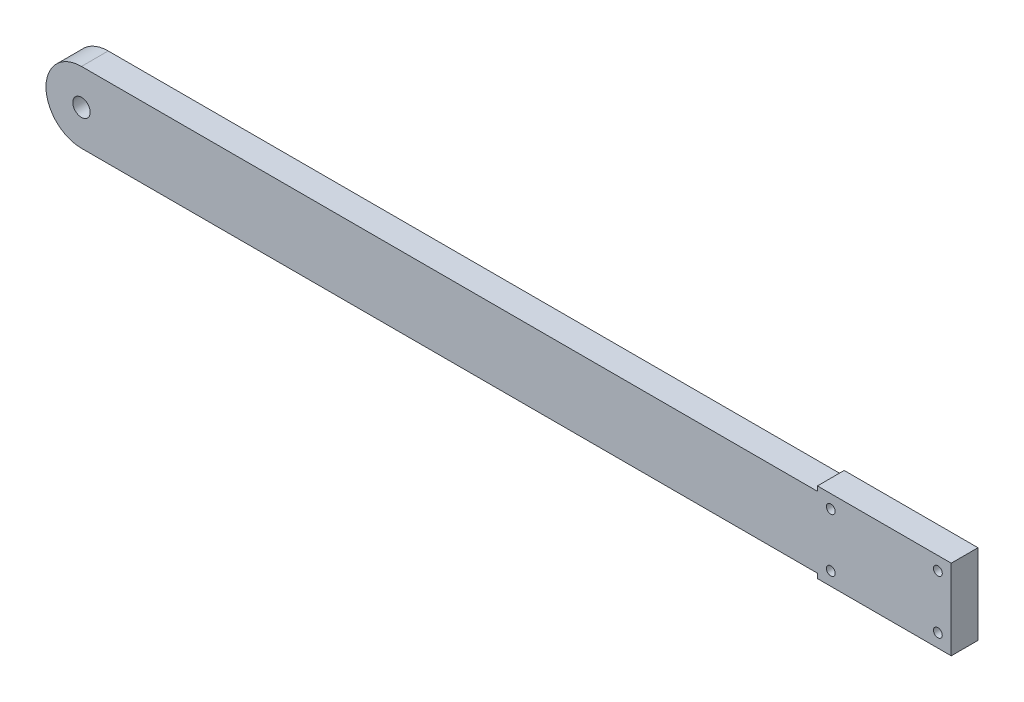
SolidWorks part; units mm, degrees
ref_plane "Front Plane" through (0, 0, 0) normal (0, 0, 1) x (1, 0, 0)
ref_plane "Top Plane" through (0, 0, 0) normal (0, 1, 0) x (1, 0, 0)
ref_plane "Right Plane" through (0, 0, 0) normal (1, 0, 0) x (0, 0, -1)
sketch "Sketch1" plane through (0, 0, 0) normal (0, 0, 1) x (1, 0, 0)
  line L0 (0, 0) -> (300, 0) construction
  line L1 (0, 13.25) -> (300, 13.25)
  line L2 (0, -13.25) -> (300, -13.25)
  line L3 (280, 10) -> (320, 10) construction
  line L4 (275, -15) -> (325, -15)
  line L5 (275, -15) -> (275, 15)
  line L6 (275, 15) -> (325, 15)
  line L7 (325, -15) -> (325, 15)
  line L8 (300, 15) -> (300, -15) construction
  line L9 (275, 0) -> (325, 0) construction
  line L10 (280, 10) -> (280, -10) construction
  arc A0 (0, 13.25) -> (0, -13.25) centre (0, 0) ccw
  arc A1 (300, -13.25) -> (300, 13.25) centre (300, 0) ccw
  circle A2 centre (0, 0) radius 3.25
  circle A3 centre (280, 10) radius 1.65
  circle A4 centre (320, 10) radius 1.65
  circle A5 centre (280, -10) radius 1.65
  circle A6 centre (320, -10) radius 1.65
  point P3 (150, 0)
  point P10 (300, 0)
  point P21 (300, 10)
  point P25 (280, 0)
  point P26 (300, 0)
  dimension "D1" = 6.5
  dimension "D2" = 10
  dimension "D4" = 3.3
  dimension "D3" = 300
  dimension "D5" = 40
  dimension "D6" = 20
  dimension "D7" = 5
  dimension "D8" = 5
extrude "Main Arm" add sketch "Sketch1" along normal blind 10 contours L1 A0 L2 L5 A2 | L2 A1 L1 L5 A3 A5 | A1 L2 L5 L4 L7 L6 L1 A6 A4 region at (132.8643, 0, 0) region at (275.5831, 14.125, 0) region at (293.065, 0, 0)
